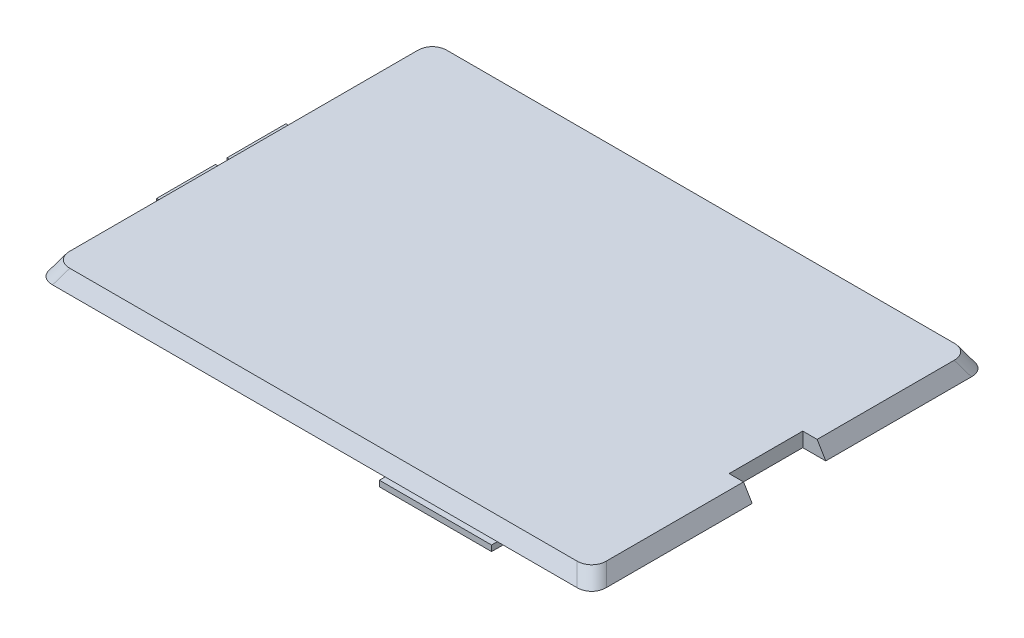
SolidWorks part; units mm, degrees
ref_plane "Front Plane" through (0, 0, 0) normal (0, 0, 1) x (1, 0, 0)
ref_plane "Top Plane" through (0, 0, 0) normal (0, 1, 0) x (1, 0, 0)
ref_plane "Right Plane" through (0, 0, 0) normal (1, 0, 0) x (0, 0, -1)
sketch "Sketch1" plane through (0, 0, 0) normal (0, 1, 0) x (1, 0, 0)
  line L1 (-48.15, -34.3) -> (48.15, -34.3)
  line L2 (-48.15, -34.3) -> (-48.15, 34.3)
  line L3 (-48.15, 34.3) -> (48.15, 34.3)
  line L4 (48.15, -34.3) -> (48.15, 34.3)
  line L5 (-48.15, -34.3) -> (48.15, 34.3) construction
  line L6 (-48.15, 34.3) -> (48.15, -34.3) construction
  point P0 (0, 0)
  dimension "D1" = 68.6
  dimension "D2" = 96.3
ref_plane "Plane1" through (0, 2.5, 0) normal (0, 1, 0) x (1, 0, 0)
sketch "Sketch2" plane through (0, 2.5, 0) normal (0, 1, 0) x (1, 0, 0)
  line L0 (48.15, -34.3) -> (48.15, 34.3) construction
  line L1 (-46.65, -32.8) -> (46.65, -32.8)
  line L2 (-46.65, -32.8) -> (-46.65, 32.8)
  line L3 (-46.65, 32.8) -> (46.65, 32.8)
  line L4 (46.65, -32.8) -> (46.65, 32.8)
  line L5 (-46.65, -32.8) -> (46.65, 32.8) construction
  line L6 (-46.65, 32.8) -> (46.65, -32.8) construction
  line L7 (-48.15, 34.3) -> (48.15, 34.3) construction
  point P0 (0, 0)
  dimension "D1" = 1.5
  dimension "D2" = 1.5
loft "Loft1" add profiles "Sketch1", "Sketch2"
sketch "Sketch3" plane through (0, 0, 0) normal (0, -1, 0) x (1, 0, 0)
  line L0 (48.15, 34.3) -> (48.15, -34.3) construction
  line L1 (44.15, -6.4) -> (48.15, -6.4)
  line L2 (44.15, -6.4) -> (44.15, 6.4)
  line L3 (44.15, 6.4) -> (48.15, 6.4)
  line L4 (48.15, -6.4) -> (48.15, 6.4)
  line L5 (44.15, -6.4) -> (48.15, 6.4) construction
  line L6 (44.15, 6.4) -> (48.15, -6.4) construction
  point P0 (46.15, 0)
  point P5 (0, 0)
  dimension "D1" = 4
  dimension "D2" = 12.8
extrude "Cut-Extrude1" cut sketch "Sketch3" against normal through all
sketch "Sketch4" plane through (0, 0, 0) normal (0, -1, 0) x (1, 0, 0)
  line L0 (-48.15, 34.3) -> (48.15, 34.3) construction
  line L1 (11.25, 31) -> (30.75, 31)
  line L2 (11.25, 31) -> (11.25, 33)
  line L3 (11.25, 33) -> (30.75, 33)
  line L4 (30.75, 31) -> (30.75, 33)
  line L5 (11.25, 31) -> (30.75, 33) construction
  line L6 (11.25, 33) -> (30.75, 31) construction
  line L7 (11.25, -33) -> (30.75, -33)
  line L8 (11.25, -33) -> (11.25, -31)
  line L9 (11.25, -31) -> (30.75, -31)
  line L10 (30.75, -33) -> (30.75, -31)
  line L11 (11.25, -33) -> (30.75, -31) construction
  line L12 (11.25, -31) -> (30.75, -33) construction
  line L13 (-46.85, -7.15) -> (-45.35, -7.15)
  line L14 (-46.85, -7.15) -> (-46.85, 7.15)
  line L15 (-46.85, 7.15) -> (-45.35, 7.15)
  line L16 (-45.35, -7.15) -> (-45.35, 7.15)
  line L17 (-46.85, -7.15) -> (-45.35, 7.15) construction
  line L18 (-46.85, 7.15) -> (-45.35, -7.15) construction
  line L19 (48.15, -34.3) -> (-48.15, -34.3) construction
  line L20 (-48.15, -34.3) -> (-48.15, 34.3) construction
  line L21 (48.15, 34.3) -> (48.15, 6.4) construction
  point P0 (21, 32)
  point P5 (21, -32)
  point P10 (-46.1, 0)
  point P15 (0, 0)
  point P21 (-36.733, 0)
  point P26 (0, 0)
  point P27 (21, -27.571)
  dimension "D1" = 1.3
  dimension "D2" = 1.3
  dimension "D3" = 1.3
  dimension "D4" = 17.4
  dimension "D5" = 19.5
  dimension "D6" = 2
  dimension "D7" = 14.3
  dimension "D8" = 1.5
extrude "Boss-Extrude1" add sketch "Sketch4" along normal blind 1
sketch "Sketch5" plane through (0, -1, 0) normal (0, -1, 0) x (1, 0, 0)
  line L0 (-45.35, -7.15) -> (-45.35, 7.15) construction
  line L1 (-50.55, -11.25) -> (-45.35, -11.25)
  line L2 (-50.55, -11.25) -> (-50.55, 11.25) construction
  line L3 (-50.55, 11.25) -> (-45.35, 11.25)
  line L4 (-45.35, -11.25) -> (-45.35, 11.25)
  line L5 (-50.55, -11.25) -> (-45.35, 11.25) construction
  line L6 (-50.55, 11.25) -> (-45.35, -11.25) construction
  line L7 (-50.55, 11.25) -> (-50.55, 1)
  line L8 (-50.55, -11.25) -> (-50.55, -1)
  line L9 (-50.55, 1) -> (-48.55, 1)
  line L10 (-48.55, 1) -> (-48.55, -1)
  line L11 (-48.55, -1) -> (-50.55, -1)
  point P0 (-47.95, 0)
  point P5 (-48.55, 0)
  point P13 (0, 0)
  point P14 (-48.1811, -1)
  point P15 (-49.2895, -1)
  dimension "D1" = 22.5
  dimension "D2" = 5.2
  dimension "D3" = 2
  dimension "D4" = 4
extrude "Boss-Extrude2" add sketch "Sketch5" along normal blind 0.6
sketch "Sketch6" plane through (0, -1, 0) normal (0, -1, 0) x (1, 0, 0)
  line L0 (48.15, -34.3) -> (-48.15, -34.3) construction
  line L1 (11.25, 31) -> (30.75, 31)
  line L2 (11.25, 31) -> (11.25, 34.3)
  line L3 (11.25, 34.3) -> (30.75, 34.3)
  line L4 (30.75, 31) -> (30.75, 34.3)
  line L5 (11.25, -31) -> (30.75, -31)
  line L6 (11.25, -31) -> (11.25, -34.3)
  line L7 (11.25, -34.3) -> (30.75, -34.3)
  line L8 (30.75, -31) -> (30.75, -34.3)
  line L9 (30.75, -33) -> (30.75, -31) construction
  line L10 (-48.15, 34.3) -> (48.15, 34.3) construction
  line L11 (30.75, 31) -> (30.75, 33) construction
  point P9 (0, 0)
  point P15 (0, 0)
extrude "Boss-Extrude3" add sketch "Sketch6" along normal blind 1
fillet "Fillet1" radius 3 4 edges
